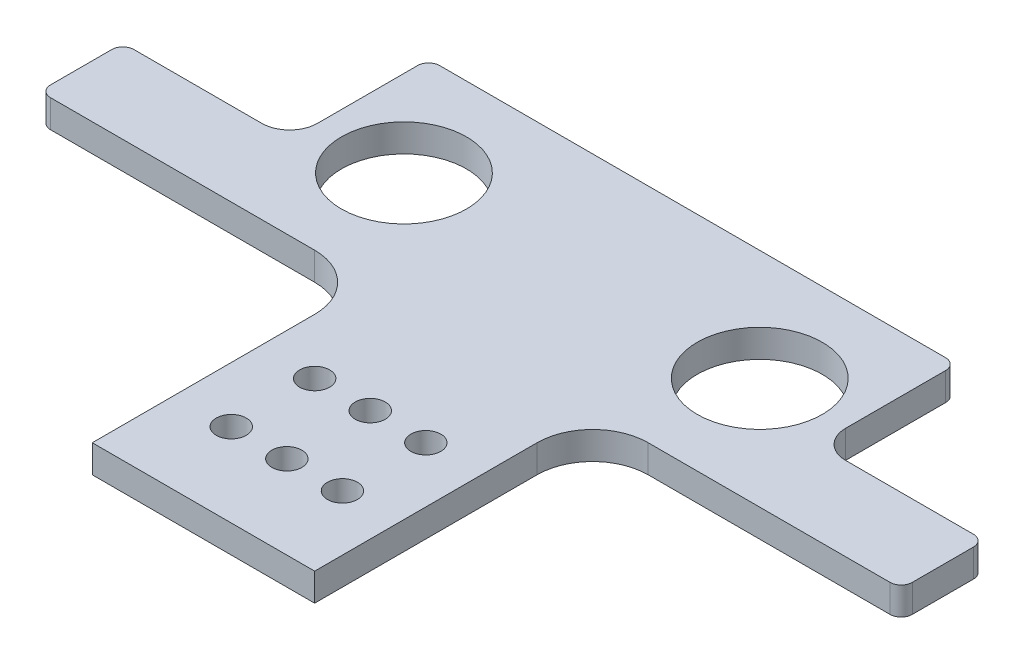
SolidWorks part; units mm, degrees
ref_plane "Front Plane" through (0, 0, 0) normal (0, 0, 1) x (1, 0, 0)
ref_plane "Top Plane" through (0, 0, 0) normal (0, 1, 0) x (1, 0, 0)
ref_plane "Right Plane" through (0, 0, 0) normal (1, 0, 0) x (0, 0, -1)
sketch "Sketch2" plane through (0, 0, 0) normal (0, 1, 0) x (1, 0, 0)
  line L1 (-52.4007, -9.869) -> (68.2493, -9.869)
  line L2 (-52.4007, -9.869) -> (-52.4007, 40.931)
  line L3 (-52.4007, 40.931) -> (68.2493, 40.931)
  line L4 (68.2493, -9.869) -> (68.2493, 40.931)
  line L5 (-52.4007, -9.869) -> (68.2493, 40.931) construction
  line L6 (-52.4007, 40.931) -> (68.2493, -9.869) construction
  point P0 (7.9243, 15.531)
  dimension "D1" = 120.65
  dimension "D2" = 50.8
extrude "Boss-Extrude1" add sketch "Sketch2" along normal blind 6.35
ref_plane "Plane1" through (7.9243, 0, 0) normal (1, 0, 0) x (0, 0, -1)
sketch "Sketch3" plane through (0, 6.35, 0) normal (0, 1, 0) x (1, 0, 0)
  line L0 (7.9243, -3.4925) -> (7.9243, 3.4925) construction
  line L2 (68.2493, 40.931) -> (-52.4007, 40.931) construction
  circle A0 centre (-32.7157, 15.6148) radius 14.2875
  dimension "D1" = 28.575
  dimension "D2" = 40.64
  dimension "D3" = 25.3163
extrude "Cut-Extrude1" cut sketch "Sketch3" against normal blind 6.35 contours A0
mirror "Mirror1" about plane through (7.9243, 0, 0) normal (1, 0, 0) of "Cut-Extrude1"
sketch "Sketch6" plane through (0, 6.35, 0) normal (0, 1, 0) x (1, 0, 0)
  line L0 (-52.4007, 40.931) -> (-52.4007, -9.869) construction
  line L1 (-90.5007, 9.181) -> (-52.4007, 9.181)
  line L2 (-90.5007, 9.181) -> (-90.5007, -9.869)
  line L3 (-90.5007, -9.869) -> (-52.4007, -9.869)
  line L4 (-52.4007, 9.181) -> (-52.4007, -9.869)
  line L5 (-52.4007, -9.869) -> (68.2493, -9.869) construction
  dimension "D1" = 38.1
  dimension "D2" = 0
  dimension "D3" = 0
  dimension "D4" = 19.05
extrude "Boss-Extrude2" add sketch "Sketch6" against normal blind 6.35
mirror "Mirror2" about plane through (7.9243, 0, 0) normal (1, 0, 0) of "Boss-Extrude2"
fillet "Fillet2" radius 6.35 2 edges at (68.2493, 3.175, -9.181) (-52.4007, 3.175, -9.181)
fillet "Fillet1" radius 2.54 6 edges at (68.2493, 3.175, -40.931) (-52.4007, 3.175, -40.931) (106.3493, 3.175, 9.869) (106.3493, 3.175, -9.181) (-90.5007, 3.175, 9.869) (-90.5007, 3.175, -9.181)
sketch "Sketch8" plane through (0, 6.35, 0) normal (0, 1, 0) x (1, 0, 0)
  line L0 (-87.9607, -9.869) -> (103.8093, -9.869) construction
  line L1 (-14.9357, -9.869) -> (35.8643, -9.869)
  line L2 (-14.9357, -9.869) -> (-14.9357, -73.369)
  line L3 (-14.9357, -73.369) -> (35.8643, -73.369)
  line L4 (35.8643, -9.869) -> (35.8643, -73.369)
  line L5 (106.3493, 6.641) -> (106.3493, -7.329) construction
  dimension "D1" = 50.8
  dimension "D2" = 63.5
  dimension "D3" = 70.485
extrude "Boss-Extrude3" add sketch "Sketch8" against normal blind 6.35 contours L3 L4 L1 L2
fillet "Fillet3" radius 12.7 2 edges at (35.8643, 3.175, 9.869) (-14.9357, 3.175, 9.869)
sketch "Sketch9" plane through (0, 6.35, 0) normal (0, 1, 0) x (1, 0, 0)
  line L0 (-14.9357, -73.369) -> (35.8643, -73.369) construction
  line L1 (-14.9357, -22.569) -> (-14.9357, -73.369) construction
  circle A0 centre (-2.2357, -54.319) radius 3.429
  dimension "D1" = 6.858
  dimension "D2" = 19.05
  dimension "D3" = 12.7
extrude "Cut-Extrude2" cut sketch "Sketch9" against normal blind 6.35
pattern_linear "LPattern1" count 3 spacing 12.7 along (1, 0, 0) count 2 spacing 19.05 along (0, 0, -1) of "Cut-Extrude2"
